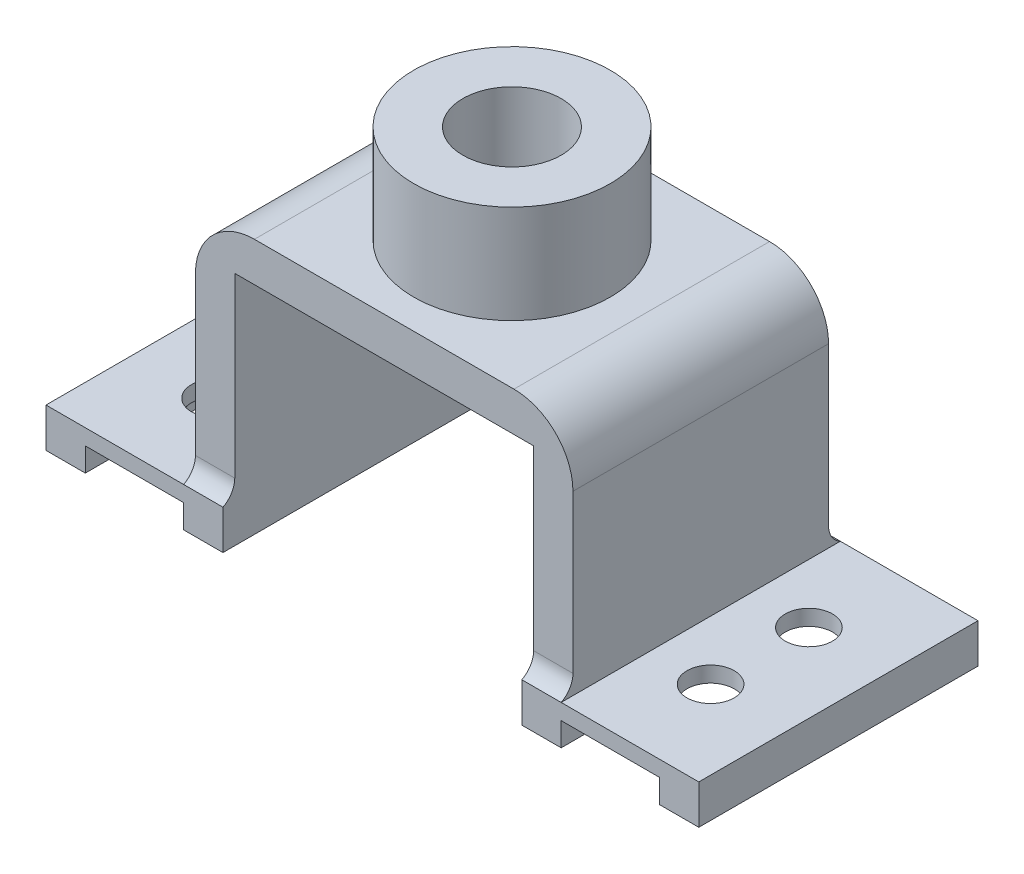
SolidWorks part; units mm, degrees
ref_plane "Front Plane" through (0, 0, 0) normal (0, 0, 1) x (1, 0, 0)
ref_plane "Top Plane" through (0, 0, 0) normal (0, 1, 0) x (1, 0, 0)
ref_plane "Right Plane" through (0, 0, 0) normal (1, 0, 0) x (0, 0, -1)
sketch "Sketch1" plane through (0, 0, 0) normal (0, 0, 1) x (1, 0, 0)
  line L0 (0, 0) -> (0, 97.1803) construction
  line L1 (-48, 70) -> (48, 70)
  line L2 (-48, 70) -> (-48, 0)
  line L3 (-48, 0) -> (48, 0)
  line L4 (48, 70) -> (48, 0)
  dimension "D1" = 96
  dimension "D2" = 70
extrude "Boss-Extrude1" add sketch "Sketch1" along normal mid plane 65 contours L1 L4 L3 L2
sketch "Sketch2" plane through (0, 0, 0) normal (0, 0, 1) x (1, 0, 0)
  line L0 (38, 0) -> (38, 10)
  line L1 (-48, 0) -> (48, 0) construction
  line L2 (38, 10) -> (83, 10)
  line L3 (83, 10) -> (83, 0)
  line L4 (83, 0) -> (73, 0)
  line L5 (73, 0) -> (73, 6)
  line L6 (73, 6) -> (48, 6)
  line L7 (48, 70) -> (48, 0) construction
  line L8 (48, 6) -> (48, 0)
  line L9 (48, 0) -> (38, 0)
  dimension "D1" = 25
  dimension "D2" = 6
  dimension "D3" = 10
  dimension "D4" = 45
  dimension "D5" = 10
extrude "Boss-Extrude2" add sketch "Sketch2" along normal mid plane 71
mirror "Mirror1" about plane through (0, 0, 0) normal (1, 0, 0) of "Boss-Extrude2"
sketch "Sketch3" plane through (0, 0, 32.5) normal (0, 0, 1) x (1, 0, 0)
  line L0 (-38, 0) -> (38, 0) construction
  line L1 (-38, 0) -> (38, 0)
  line L2 (-38, 0) -> (-38, 60)
  line L3 (-38, 60) -> (38, 60)
  line L4 (38, 0) -> (38, 60)
  line L5 (-38, 10) -> (-38, 0) construction
  line L6 (38, 10) -> (38, 0) construction
  line L7 (-48, 70) -> (48, 70) construction
  dimension "D1" = 10
extrude "Cut-Extrude1" cut sketch "Sketch3" against normal through all
fillet "Fillet1" radius 15 2 edges at (-48, 70, 0) (48, 70, 0)
fillet "Fillet2" radius 5.5 4 edges at (-43, 10, -32.5) (43, 10, -32.5) (-43, 10, 32.5) (43, 10, 32.5)
sketch "Sketch4" plane through (0, 70, 0) normal (0, 1, 0) x (1, 0, 0)
  circle A0 centre (0, 0) radius 25
  circle A1 centre (0, 0) radius 12.5
  dimension "D1" = 50
  dimension "D2" = 25
extrude "Boss-Extrude3" add sketch "Sketch4" along normal blind 25
hole_wizard "Hole1" positions "Sketch5" profile "Sketch6" legacy end condition through all
sketch "Sketch5" plane through (0, 10, 0) normal (0, 1, 0) x (1, 0, 0)
  line L0 (83, -35.5) -> (48, -35.5) construction
  point P0 (63, 12.5)
  point P2 (63, -12.5)
  point P8 (0, 0)
  dimension "D1" = 25
  dimension "D2" = 23
  dimension "D3" = 63
sketch "Sketch6" plane through (63, 10, -12.5) normal (1, 0, 0) x (0, 0, 1)
  line L0 (0, 0) -> (0, 10)
  line L1 (0, 10) -> (6, 10)
  line L2 (6, 10) -> (6, 0)
  line L3 (6, 0) -> (0, 0)
  line L4 (0, 110) -> (0, -10) construction
  dimension "Diameter" = 12
  dimension "Depth" = 10
mirror "Mirror2" about plane through (0, 0, 0) normal (1, 0, 0) of "Hole1"
